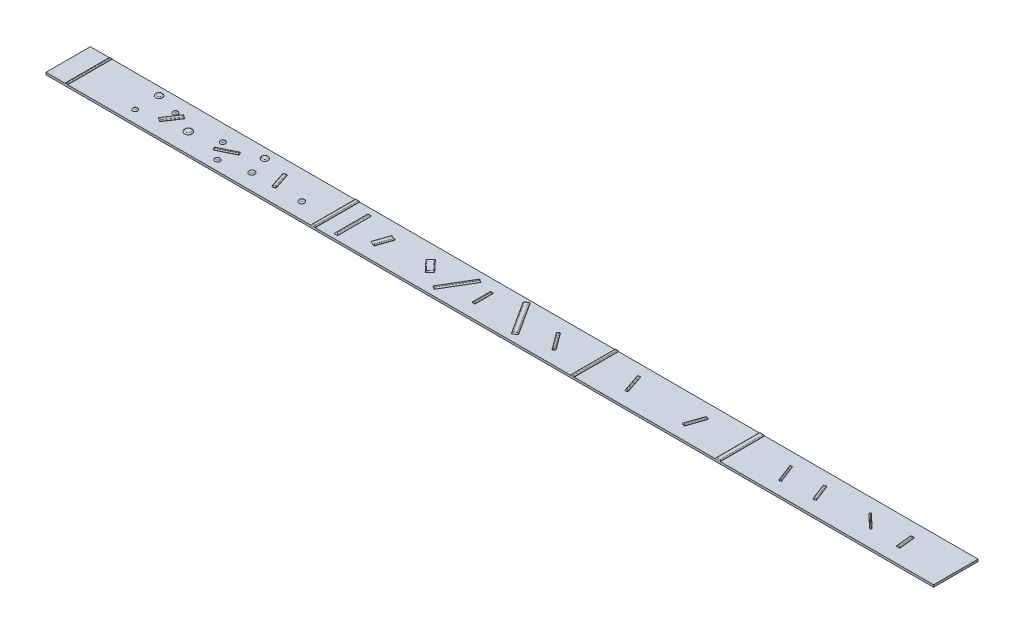
SolidWorks part; units mm, degrees
ref_plane "Alzado" through (0, 0, 0) normal (0, 0, 1) x (1, 0, 0)
ref_plane "Planta" through (0, 0, 0) normal (0, 1, 0) x (1, 0, 0)
ref_plane "Vista lateral" through (0, 0, 0) normal (1, 0, 0) x (0, 0, -1)
sketch "Croquis1" plane through (0, 0, 0) normal (0, 1, 0) x (1, 0, 0)
  line L1 (-20000, 1000) -> (20000, 1000)
  line L2 (-20000, 1000) -> (-20000, -1000)
  line L3 (-20000, -1000) -> (20000, -1000)
  line L4 (20000, 1000) -> (20000, -1000)
  line L5 (-20000, 1000) -> (20000, -1000) construction
  line L6 (-20000, -1000) -> (20000, 1000) construction
  point P0 (0, 0)
  dimension "D1" = 40000
  dimension "D2" = 2000
extrude "Saliente-Extruir1" add sketch "Croquis1" along normal blind 100
sketch "Croquis2" plane through (0, 100, 0) normal (0, 1, 0) x (1, 0, 0)
  line L0 (20000, 1000) -> (-20000, 1000) construction
  line L1 (-19123.9382, 1000) -> (-19023.9382, 1000)
  line L2 (-19123.9382, 1000) -> (-19123.9382, -1000)
  line L3 (-19123.9382, -1000) -> (-19023.9382, -1000)
  line L4 (-19023.9382, 1000) -> (-19023.9382, -1000)
  line L5 (-20000, -1000) -> (20000, -1000) construction
  line L14 (-13200.6123, -266.8851) -> (-12417.2305, 116.8122)
  line L15 (-13200.6123, -266.8851) -> (-13257.0005, -151.7593)
  line L16 (-12417.2305, 116.8122) -> (-12473.6186, 231.938)
  line L17 (-13257.0005, -151.7593) -> (-12473.6186, 231.938)
  line L23 (-8049.6553, -1000) -> (-7868.7781, -1000)
  line L24 (-8049.6553, -1000) -> (-8049.6553, 1000)
  line L25 (-8049.6553, 1000) -> (-7868.7781, 1000)
  line L26 (-7868.7781, -1000) -> (-7868.7781, 1000)
  line L30 (-4111.6032, 231.938) -> (-3644.07, -266.8851)
  line L31 (-4111.6032, 231.938) -> (-3892.0622, 437.7078)
  line L32 (-3644.07, -266.8851) -> (-3424.529, -61.1153)
  line L33 (-3892.0622, 437.7078) -> (-3424.529, -61.1153)
  line L39 (3655.3213, 1000) -> (3799.2174, 1000)
  line L40 (3655.3213, 1000) -> (3655.3213, -1000)
  line L41 (3655.3213, -1000) -> (3799.2174, -1000)
  line L42 (3799.2174, 1000) -> (3799.2174, -1000)
  line L47 (10167.1093, 1000) -> (10386.746, 1000)
  line L48 (10167.1093, 1000) -> (10167.1093, -1000)
  line L49 (10167.1093, -1000) -> (10386.746, -1000)
  line L50 (10386.746, 1000) -> (10386.746, -1000)
  line L58 (-15509.7818, -367.9789) -> (-15663.9914, -266.8851)
  line L59 (-15509.7818, -367.9789) -> (-15061.6538, 315.6007)
  line L60 (-15663.9914, -266.8851) -> (-15215.8634, 416.6945)
  line L61 (-15061.6538, 315.6007) -> (-15215.8634, 416.6945)
  line L62 (-10543.6032, 416.6945) -> (-10693.3822, 366.1476)
  line L63 (-10543.6032, 416.6945) -> (-10289.5004, -336.2551)
  line L64 (-10693.3822, 366.1476) -> (-10439.2795, -386.802)
  line L65 (-10289.5004, -336.2551) -> (-10439.2795, -386.802)
  line L66 (-5806.7253, 391.421) -> (-5586.2729, 315.6007)
  line L67 (-5806.7253, 391.421) -> (-6047.5764, -308.8684)
  line L68 (-5586.2729, 315.6007) -> (-5827.124, -384.6888)
  line L69 (-6047.5764, -308.8684) -> (-5827.124, -384.6888)
  line L70 (-1403.439, 437.7078) -> (-1403.439, -384.6888)
  line L71 (-1403.439, 437.7078) -> (-1289.1565, 437.7078)
  line L72 (-1403.439, -384.6888) -> (-1289.1565, -384.6888)
  line L73 (-1289.1565, 437.7078) -> (-1289.1565, -384.6888)
  line L74 (1682.8723, 315.6007) -> (1785.3191, 391.421)
  line L75 (1682.8723, 315.6007) -> (2232.2776, -426.7441)
  line L76 (1785.3191, 391.421) -> (2334.7244, -350.9237)
  line L77 (2232.2776, -426.7441) -> (2334.7244, -350.9237)
  line L78 (5296.7959, 492.3073) -> (5192.5023, 457.1107)
  line L79 (5296.7959, 492.3073) -> (5580.6175, -348.7042)
  line L80 (5192.5023, 457.1107) -> (5476.3239, -383.9009)
  line L81 (5580.6175, -348.7042) -> (5476.3239, -383.9009)
  line L82 (8191.4342, -426.7441) -> (8065.785, -383.9009)
  line L83 (8191.4342, -426.7441) -> (8465.8363, 378.0133)
  line L84 (8065.785, -383.9009) -> (8340.1871, 420.8565)
  line L85 (8465.8363, 378.0133) -> (8340.1871, 420.8565)
  line L86 (12135.0834, 378.0133) -> (12448.464, -426.7441)
  line L87 (12135.0834, 378.0133) -> (12222.2869, 411.9712)
  line L88 (12448.464, -426.7441) -> (12535.6674, -392.7862)
  line L89 (12222.2869, 411.9712) -> (12535.6674, -392.7862)
  line L90 (13771.057, 411.9712) -> (14066.5006, -346.7242)
  line L91 (13771.057, 411.9712) -> (13652.6133, 365.848)
  line L92 (14066.5006, -346.7242) -> (13948.0569, -392.8474)
  line L93 (13652.6133, 365.848) -> (13948.0569, -392.8474)
  line L94 (15767.3425, 315.6007) -> (16382.6253, -266.8851)
  line L95 (15767.3425, 315.6007) -> (15822.3611, 373.7172)
  line L96 (16382.6253, -266.8851) -> (16437.6439, -208.7686)
  line L97 (15822.3611, 373.7172) -> (16437.6439, -208.7686)
  line L98 (17597.9615, 373.7172) -> (17672.1274, -346.7242)
  line L99 (17597.9615, 373.7172) -> (17736.9134, 388.0216)
  line L100 (17672.1274, -346.7242) -> (17811.0792, -332.4198)
  line L101 (17736.9134, 388.0216) -> (17811.0792, -332.4198)
  point P9 (0, 0)
  point P71 (0, 0)
  dimension "D1" = 100
sketch "Croquis3" plane through (0, 100, 0) normal (0, 1, 0) x (1, 0, 0)
  circle A0 centre (-16527.7466, 627.6907) radius 152.1084
  circle A1 centre (-14473.6235, -112.749) radius 170.3882
  circle A2 centre (-11694.9842, 556.0353) radius 149.5871
  circle A3 centre (-9187.0432, -283.1372) radius 124.0966
  circle A4 centre (-16527.7466, -453.459) radius 107.7681
  circle A5 centre (-12713.0492, -561.2271) radius 114.5555
  circle A6 centre (-13274.8549, 248.7981) radius 113.8953
  circle A7 centre (-15488.6368, 322.3678) radius 109.694
  circle A8 centre (-11435.6101, -283.1372) radius 130.3581
extrude "Saliente-Extruir2" add sketch "Croquis3" along normal blind 50
fillet "Redondeo1" radius 50 9 edges at (-9187.0432, 150, 407.2337) (-11694.9842, 150, -406.4482) (-14473.6235, 150, 283.1372) (-16527.7466, 150, -475.5823) (-11435.6101, 150, 413.4953) (-12713.0492, 150, 675.7826) (-15488.6368, 150, -212.6738) (-13274.8549, 150, -134.9028) (-16527.7466, 150, 561.2271)
sketch "Croquis4" plane through (0, 100, 0) normal (0, 1, 0) x (1, 0, 0)
  line L0 (-2782.8397, -722.0882) -> (-1999.4067, 596.3722)
  line L1 (-7196.8158, 711.0209) -> (-7053.5049, 711.0209)
  line L2 (-7196.8158, 711.0209) -> (-7196.8158, -808.0748)
  line L3 (-7196.8158, -808.0748) -> (-7053.5049, -808.0748)
  line L4 (-7053.5049, 711.0209) -> (-7053.5049, -808.0748)
  line L5 (-2782.8397, -722.0882) -> (-2918.1242, -641.7018)
  line L6 (-1999.4067, 596.3722) -> (-2134.6912, 676.7586)
  line L7 (-2918.1242, -641.7018) -> (-2134.6912, 676.7586)
  line L8 (-270.1217, 768.3453) -> (694.8384, -722.0882)
  line L9 (-270.1217, 768.3453) -> (-76.0551, 893.991)
  line L10 (694.8384, -722.0882) -> (888.905, -596.4425)
  line L11 (-76.0551, 893.991) -> (888.905, -596.4425)
extrude "Saliente-Extruir3" add sketch "Croquis4" along normal blind 50
fillet "Redondeo2" radius 50 12 edges at (406.425, 150, -148.7742) (791.8717, 150, 659.2654) (212.3583, 150, -23.1285) (-173.0884, 150, -831.1681) (-2526.4077, 150, -17.5284) (-2067.049, 150, -636.5654) (-2391.1232, 150, 62.858) (-2850.4819, 150, 681.895) (-7125.1604, 150, -711.0209) (-7053.5049, 150, 48.5269) (-7125.1604, 150, 808.0748) (-7196.8158, 150, 48.5269)
extrude "Saliente-Extruir4" add sketch "Croquis2" along normal blind 50
fillet "Redondeo3" radius 40 68 edges at (17773.9963, 150, -27.8009) (17741.6033, 150, 339.572) (17635.0444, 150, -13.4965) (17667.4374, 150, -380.8694) (16130.0025, 150, -82.4743) (16410.1346, 150, 237.8268) (16074.9839, 150, -24.3578) (15794.8518, 150, -344.6589) (13918.7788, 150, -32.6235) (14007.2787, 150, 369.7858) (13800.3351, 150, 13.4997) (13711.8351, 150, -388.9096) (12378.9771, 150, -9.5925) (12492.0657, 150, 409.7651) (12291.7737, 150, 24.3654) (12178.6851, 150, -394.9922) (3727.2693, 150, -1000) (3799.2174, 150, 0) (3727.2693, 150, 1000) (3655.3213, 150, 0) (10276.9277, 150, -1000) (10386.746, 150, 0) (10276.9277, 150, 1000) (10167.1093, 150, 0) (8128.6096, 150, 405.3225) (8202.986, 150, -18.4778) (8403.0117, 150, -399.4349) (8328.6352, 150, 24.3654) (5528.4707, 150, 366.3025) (5334.4131, 150, -36.6049) (5244.6491, 150, -474.709) (5438.7067, 150, -71.8015) (1734.0957, 150, -353.5108) (2060.0218, 150, -20.2487) (2283.501, 150, 388.8339) (1957.5749, 150, 55.5717) (-1289.1565, 150, -26.5095) (-1346.2977, 150, 384.6888) (-1403.439, 150, -26.5095) (-1346.2977, 150, -437.7078) (-3658.2956, 150, -188.2963) (-3534.2995, 150, 164.0002) (-3877.8366, 150, 17.4736) (-4001.8327, 150, -334.8229) (-5696.4991, 150, -353.5108) (-5706.6985, 150, 34.544) (-5937.3502, 150, 346.7786) (-5927.1508, 150, -41.2763) (-10364.39, 150, 361.5285) (-10566.3309, 150, 10.3272) (-10618.4927, 150, -391.421) (-10416.5518, 150, -40.2197) (-12865.3096, 150, -40.0894) (-12445.4246, 150, -174.3751) (-12808.9214, 150, 75.0365) (-13228.8064, 150, 209.3222) (-15586.8866, 150, 317.432) (-15439.9274, 150, -74.9047) (-15138.7586, 150, -366.1476) (-15285.7178, 150, 26.1891) (-19073.9382, 150, -1000) (-19023.9382, 150, 0) (-19073.9382, 150, 1000) (-19123.9382, 150, 0) (-7959.2167, 150, -1000) (-7868.7781, 150, 0) (-7959.2167, 150, 1000) (-8049.6553, 150, 0)
